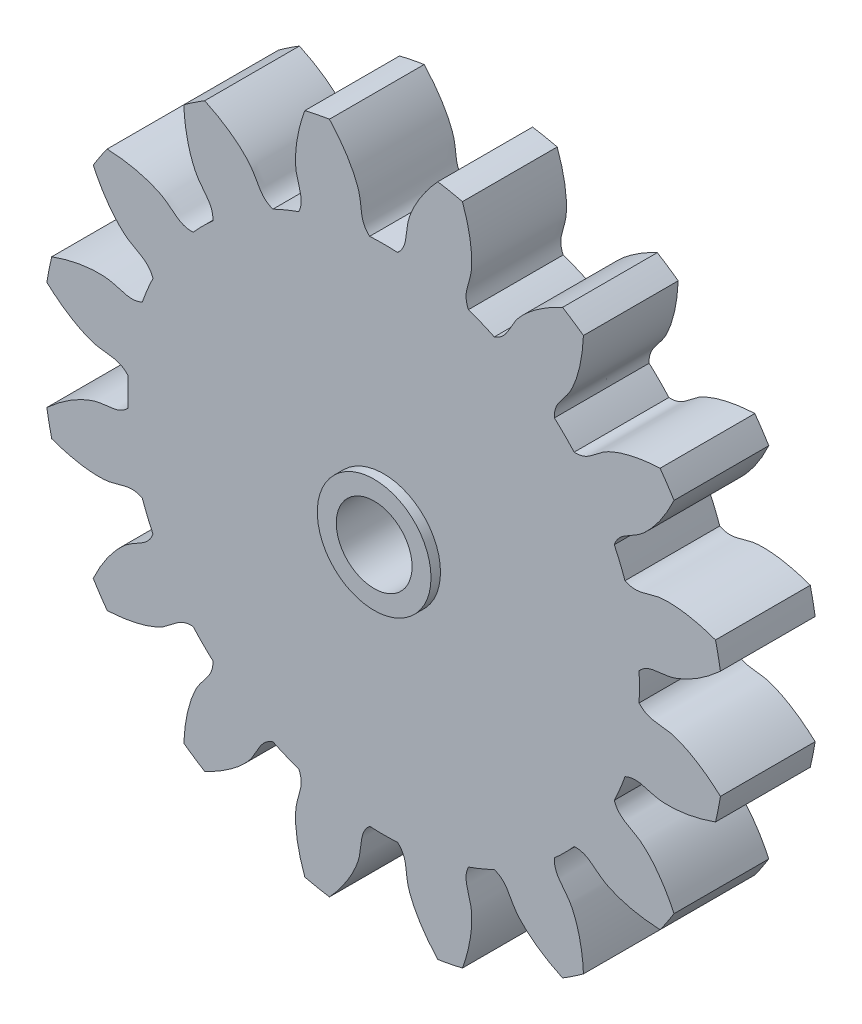
SolidWorks part; units mm, degrees
ref_plane "前视基准面" through (0, 0, 0) normal (0, 0, 1) x (1, 0, 0)
ref_plane "上视基准面" through (0, 0, 0) normal (0, 1, 0) x (1, 0, 0)
ref_plane "右视基准面" through (0, 0, 0) normal (1, 0, 0) x (0, 0, -1)
sketch "草图1" plane through (0, 0, 0) normal (0, 0, 1) x (1, 0, 0)
  circle A0 centre (0, 0) radius 18
extrude "凸台-拉伸1" add sketch "草图1" along normal blind 5
ref_axis "基准轴1" through (0, 0, -0.25) along (0, 0, 1)
sketch "草图2" plane through (0, 0, 0) normal (0, 0, 1) x (1, 0, 0)
  line L0 (0, 0) -> (0, 18) construction
  circle A0 centre (0, 0) radius 18 construction
  arc A1 (0.7374, 13.4798) -> (-0.7374, 13.4798) centre (0, 0) ccw
  arc A2 (6.2436, 20.3255) -> (-6.2436, 20.3255) centre (0, 0) ccw
  spline S0 degree 3 poles (0.7374, 13.4798) (1.2659, 13.9456) (1.1478, 14.5799) (1.2896, 15.1736) (1.3024, 15.2231) (1.3179, 15.2781) (1.3362, 15.3385) (1.3575, 15.4043) (1.3821, 15.4754) (1.4103, 15.5515) (1.4421, 15.6327) (1.4779, 15.7188) (1.5178, 15.8097) (1.562, 15.9052) (1.6108, 16.0052) (1.6643, 16.1095) (1.7227, 16.2181) (1.7862, 16.3307) (1.8551, 16.4472) (1.9294, 16.5675) (2.0094, 16.6912) (2.0951, 16.8184) (2.1869, 16.9487) (2.2848, 17.082) (2.3891, 17.218) (2.4997, 17.3567) (2.617, 17.4978) (2.741, 17.641) (2.8719, 17.7862) (3.0098, 17.9331) (3.1547, 18.0816) (3.3069, 18.2313) (3.4665, 18.3821) (3.6334, 18.5337) (3.8079, 18.6859) (3.9901, 18.8384) (4.1799, 18.9911) (4.3775, 19.1436) (4.5829, 19.2957) (4.7963, 19.4471) (5.0176, 19.5976) (5.2469, 19.7469) (5.4842, 19.8948) (5.8149, 20.0918) (6.07, 20.2335) (6.2436, 20.3255) knots 0 0 0 0 0.190533 0.195487 0.201101 0.207376 0.214312 0.221908 0.230164 0.239081 0.248659 0.258897 0.269795 0.281354 0.293574 0.306454 0.319995 0.334196 0.349058 0.36458 0.380763 0.397606 0.41511 0.433274 0.452099 0.471584 0.49173 0.512536 0.534003 0.556131 0.578919 0.602367 0.626476 0.651246 0.676676 0.702766 0.729517 0.756929 0.785001 0.813733 0.843127 0.87318 0.903894 0.935269 1 1 1 1
  spline S1 degree 3 poles (-0.7374, 13.4798) (-1.2659, 13.9456) (-1.1478, 14.5799) (-1.2896, 15.1736) (-1.3024, 15.2231) (-1.3179, 15.2781) (-1.3362, 15.3385) (-1.3575, 15.4043) (-1.3821, 15.4754) (-1.4103, 15.5515) (-1.4421, 15.6327) (-1.4779, 15.7188) (-1.5178, 15.8097) (-1.562, 15.9052) (-1.6108, 16.0052) (-1.6643, 16.1095) (-1.7227, 16.2181) (-1.7862, 16.3307) (-1.8551, 16.4472) (-1.9294, 16.5675) (-2.0094, 16.6912) (-2.0951, 16.8184) (-2.1869, 16.9487) (-2.2848, 17.082) (-2.3891, 17.218) (-2.4997, 17.3567) (-2.617, 17.4978) (-2.741, 17.641) (-2.8719, 17.7862) (-3.0098, 17.9331) (-3.1547, 18.0816) (-3.3069, 18.2313) (-3.4665, 18.3821) (-3.6334, 18.5337) (-3.8079, 18.6859) (-3.9901, 18.8384) (-4.1799, 18.9911) (-4.3775, 19.1436) (-4.5829, 19.2957) (-4.7963, 19.4471) (-5.0176, 19.5976) (-5.2469, 19.7469) (-5.4842, 19.8948) (-5.8149, 20.0918) (-6.07, 20.2335) (-6.2436, 20.3255) knots 0 0 0 0 0.190533 0.195487 0.201101 0.207376 0.214312 0.221908 0.230164 0.239081 0.248659 0.258897 0.269795 0.281354 0.293574 0.306454 0.319995 0.334196 0.349058 0.36458 0.380763 0.397606 0.41511 0.433274 0.452099 0.471584 0.49173 0.512536 0.534003 0.556131 0.578919 0.602367 0.626476 0.651246 0.676676 0.702766 0.729517 0.756929 0.785001 0.813733 0.843127 0.87318 0.903894 0.935269 1 1 1 1
extrude "切除-拉伸1" cut sketch "草图2" along normal through all
pattern_circular "阵列(圆周)1" count 16 every 22.5 about axis through (0, 0, -0.25) along (0, 0, 1) of "切除-拉伸1"
sketch "草图3" plane through (0, 0, 0) normal (0, 0, 1) x (1, 0, 0)
  circle A0 centre (0, 0) radius 16 construction
  circle A1 centre (0, 0) radius 16.25 construction
  dimension "D1" = 32.5
  dimension "Dn" = 32
sketch "草图4" plane through (0, 0, 5) normal (0, 0, 1) x (1, 0, 0)
  circle A0 centre (0, 0) radius 3
  dimension "D1" = 6
extrude "凸台-拉伸2" add sketch "草图4" along normal blind 0.5
sketch "草图5" plane through (0, 0, 5.5) normal (0, 0, 1) x (1, 0, 0)
  circle A0 centre (0, 0) radius 2
  dimension "D1" = 4
extrude "切除-拉伸2" cut sketch "草图5" against normal through all
chamfer "倒角1" distance 0.5 angle 45 1 edges at (2, 0, 0)
